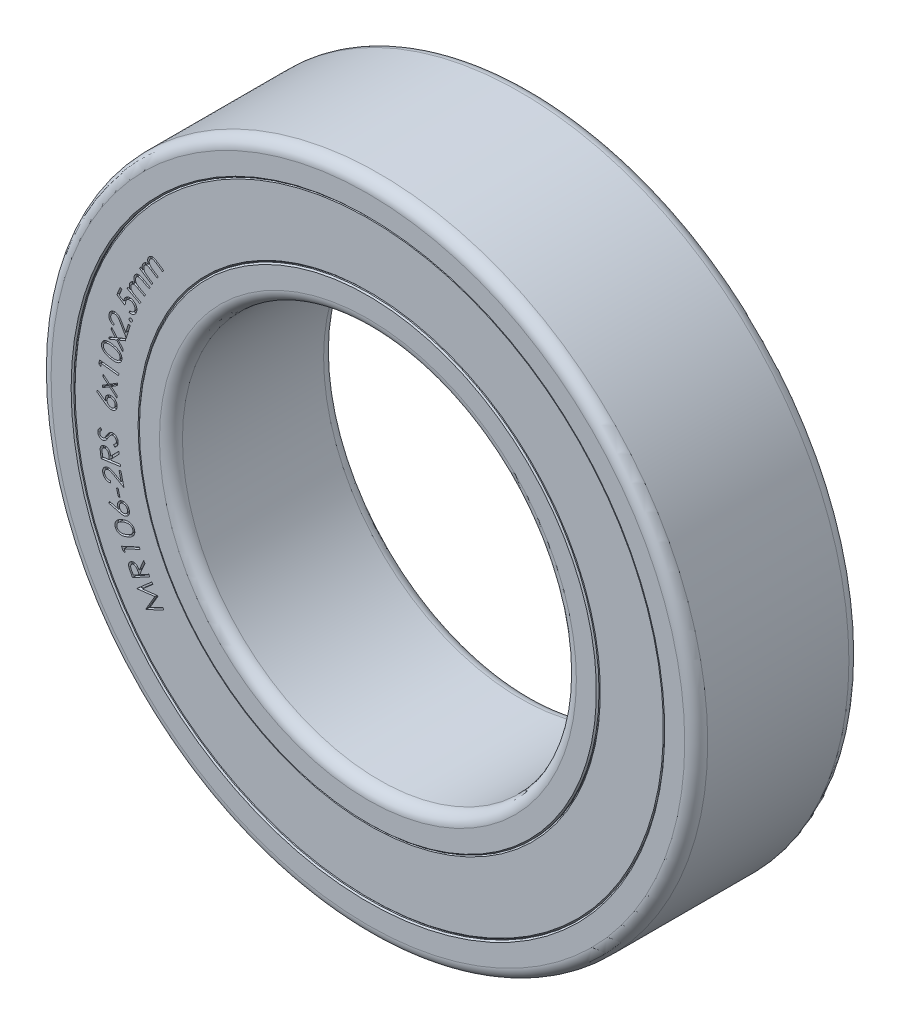
SolidWorks part; units mm, degrees
material "AISI 316 Annealed Stainless Steel Bar (SS)"
ref_plane "Front" through (0, 0, 0) normal (0, 0, 1) x (1, 0, 0)
ref_plane "Top" through (0, 0, 0) normal (0, 1, 0) x (1, 0, 0)
ref_plane "Right" through (0, 0, 0) normal (1, 0, 0) x (0, 0, -1)
sketch "LAYOUT R" plane through (0, 0, 0) normal (1, 0, 0) x (0, 0, -1)
  line L0 (-1.25, 3) -> (1.25, 3)
  line L1 (1.25, -5) -> (-1.25, -5) construction
  line L2 (1.25, -5) -> (1.25, 5) construction
  line L3 (1.25, 5) -> (-1.25, 5)
  line L4 (-1.25, -5) -> (-1.25, 5) construction
  line L5 (1.25, -5) -> (-1.25, 5) construction
  line L6 (1.25, 5) -> (-1.25, -5) construction
  line L7 (-1.25, 3.5) -> (1.25, 3.5)
  line L8 (-1.25, 4.5) -> (1.25, 4.5)
  line L11 (-17.5, 0) -> (17.5, 0) construction
  line L12 (-1.25, 5) -> (-1.25, 4.5)
  line L13 (1.25, 5) -> (1.25, 4.5)
  line L14 (-1.25, 4.5) -> (-1.25, 3.5)
  line L15 (1.25, 4.5) -> (1.25, 3.5)
  line L16 (-1.25, 3.5) -> (-1.25, 3)
  line L17 (1.25, 3.5) -> (1.25, 3)
  line L18 (-1.23, 4.5) -> (-1.23, 3.5)
  line L19 (1.23, 4.5) -> (1.23, 3.5)
  point P0 (0, 0)
  point P15 (0, 0)
  dimension "D1" = 2.5
  dimension "D2" = 10
  dimension "D3" = 3
  dimension "D6" = 0.02
  dimension "D7" = 0.02
  dimension "D4" = 3.5
  dimension "D5" = 4.5
sketch "Sketch R, INNER BODY" plane through (0, 0, 0) normal (1, 0, 0) x (0, 0, -1)
  line L0 (-1.25, 3) -> (1.25, 3) construction
  line L2 (-1.25, 3.5) -> (1.25, 3.5) construction
  line L4 (-1.25, 3) -> (1.25, 3)
  line L6 (-1.25, 3.5) -> (1.25, 3.5)
  line L8 (1.25, 3.5) -> (1.25, 3) construction
  line L9 (-1.25, 3.5) -> (-1.25, 3) construction
  line L10 (1.25, 3.5) -> (1.25, 3)
  line L11 (-1.25, 3.5) -> (-1.25, 3)
  line L12 (-17.5, 0) -> (17.5, 0) construction
  line L13 (-17.5, 0) -> (17.5, 0) construction
sketch "Sketch R, OUTER BODY" plane through (0, 0, 0) normal (1, 0, 0) x (0, 0, -1)
  line L2 (-1.25, 4.5) -> (1.25, 4.5) construction
  line L3 (1.25, 5) -> (-1.25, 5) construction
  line L6 (-1.25, 4.5) -> (1.25, 4.5)
  line L7 (1.25, 5) -> (-1.25, 5)
  line L8 (-17.5, 0) -> (17.5, 0) construction
  line L9 (-17.5, 0) -> (17.5, 0) construction
  line L10 (1.25, 5) -> (1.25, 4.5) construction
  line L11 (-1.25, 5) -> (-1.25, 4.5) construction
  line L12 (1.25, 5) -> (1.25, 4.5)
  line L13 (-1.25, 5) -> (-1.25, 4.5)
sketch "Sketch R, SEAL FACES" plane through (0, 0, 0) normal (1, 0, 0) x (0, 0, -1)
  line L0 (-17.5, 0) -> (17.5, 0) construction
  line L1 (-17.5, 0) -> (17.5, 0) construction
  line L3 (-1.25, 3.5) -> (1.25, 3.5) construction
  line L5 (-1.25, 4.5) -> (1.25, 4.5) construction
  line L7 (-1.23, 3.5) -> (1.23, 3.5)
  line L9 (-1.23, 4.5) -> (1.23, 4.5)
  line L10 (1.23, 4.5) -> (1.23, 3.5) construction
  line L11 (-1.23, 4.5) -> (-1.23, 3.5) construction
  line L12 (1.23, 4.5) -> (1.23, 3.5)
  line L13 (-1.23, 4.5) -> (-1.23, 3.5)
revolve "Revolve INNER BODY" add sketch "Sketch R, INNER BODY" angle 360 about L13
fillet "Fillet INNER BODY" radius 0.175 2 edges at (3, 0, 1.25) (3, 0, -1.25)
chamfer "Chamfer INNER BODY" distance 0.02 angle 45 2 edges at (3.5, 0, -1.25) (3.5, 0, 1.25)
revolve "Revolve OUTER BODY" add sketch "Sketch R, OUTER BODY" angle 360 about L9
fillet "Fillet OUTER BODY" radius 0.175 2 edges at (5, 0, -1.25) (5, 0, 1.25)
chamfer "Chamfer OUTER BODY" distance 0.02 angle 45 2 edges at (4.5, 0, 1.25) (4.5, 0, -1.25)
revolve "Revolve SEALS" add sketch "Sketch R, SEAL FACES" angle 360 about L1
chamfer "Chamfer SEALS" distance 0.02 angle 45 4 edges at (3.5, 0, -1.23) (4.5, 0, -1.23) (4.5, 0, 1.23) (3.5, 0, 1.23)
sketch "Sketch TEXT RADIUS 1 — MANUALLY ASSIGN TEXT AND FONT SIZE (FROM EQUATIONS)" plane through (0, 0, 1.23) normal (0, 0, 1) x (1, 0, 0)
  circle A0 centre (0, 0) radius 3.85 construction
  text T0 "MR106-2RS  6x10x2.5mm" font "Century Gothic" height 0.3
  dimension "D1" = 7.7
extrude "Cut-Extrude SEAL LABEL 1" cut sketch "Sketch TEXT RADIUS 1 — MANUALLY ASSIGN TEXT AND FONT SIZE (FROM EQUATIONS)" against normal blind 0.05
sketch "Sketch TEXT RADIUS 2 — MANUALLY ASSIGN TEXT AND FONT SIZE (FROM EQUATIONS)" plane through (0, 0, -1.23) normal (0, 0, -1) x (-1, 0, 0)
  circle A0 centre (0, 0) radius 3.85 construction
  text T0 "MR106-2RS  6x10x2.5mm" font "Century Gothic" height 0.3
  dimension "D1" = 7.7
extrude "Cut-Extrude SEAL LABEL 2" cut sketch "Sketch TEXT RADIUS 2 — MANUALLY ASSIGN TEXT AND FONT SIZE (FROM EQUATIONS)" against normal blind 0.05
equation "\"_i__BORE\"= 6"
equation "\"_i__OUTSIDE_DIAMETER\"= 10"
equation "\"_i__WIDTH\"= 2.5"
equation "\"_i_optional__TEXT_RADIUS_ADJUSTMENT\"= 0"
equation "\"_output__FONT_SIZE_mm\"= \"BODY_SPAN__SEAL__OF_RADIUS\" * \"param__FONT_SIZE_RATIO\"'MANUALLY ASSIGN TO FONT"
equation "\"BODY__HALF_WIDTH\"= \"_i__WIDTH\" / 2"
equation "\"BODY_SPAN___OF_DIAMETER\"= \"_i__OUTSIDE_DIAMETER\" - \"_i__BORE\""
equation "\"BODY_SPAN___OF_RADIUS\"= \"BODY_SPAN___OF_DIAMETER\" / 2"
equation "\"BODY_SPAN__BORE_AND_OD__OF RADIUS\"= ( \"BODY_SPAN___OF_RADIUS\" - \"BODY_SPAN__SEAL__OF_RADIUS\" ) / 2"
equation "\"BODY_SPAN__SEAL__OF_RADIUS\"= \"BODY_SPAN___OF_RADIUS\" * \"param__SEAL_PANEL_SPAN__RATIO_OF_BODY_RADIAN\""
equation "\"BORE__RADIUS\"= \"_i__BORE\" / 2"
equation "\"CORNER_RADII\"= \"_i__WIDTH\" * \"param__CORNER_RADII__ISO_MAX_RATIO_TO_WIDTH\""
equation "\"param__CORNER_RADII__ISO_MAX_RATIO_TO_WIDTH\"= 0.07'WHERE WIDTH IS LESS THAN DIAMETER"
equation "\"param__FONT_SIZE_RATIO\"= 0.3"
equation "\"param__SEAL_FACE_INSET__RATIO_OF_WIDTH\"= .01"
equation "\"param__SEAL_PANEL_SPAN__RATIO_OF_BODY_RADIAN\"= 0.5"
equation "\"param__SIDE_CHAMFERS__RATIO_TO_OD\"= 1 / 500"
equation "\"RING_INNER__OUTSIDE_RADIUS\"= \"BORE__RADIUS\" + \"BODY_SPAN__BORE_AND_OD__OF RADIUS\""
equation "\"RING_OUTER__OUTSIDE_RADIUS\"= ( \"_i__OUTSIDE_DIAMETER\" / 2 ) - \"BODY_SPAN__BORE_AND_OD__OF RADIUS\""
equation "\"SEAL_FACE_INSET\"= \"_i__WIDTH\" * \"param__SEAL_FACE_INSET__RATIO_OF_WIDTH\""
equation "\"SIDE_FACE_AND_SEAL_CHAMFERS\"= \"_i__OUTSIDE_DIAMETER\" * \"param__SIDE_CHAMFERS__RATIO_TO_OD\""
equation "\"TEXT_RADIUS\"= \"_i__BORE\" + ( \"BODY_SPAN___OF_DIAMETER\" / 2 ) - \"_output__FONT_SIZE_mm\" + \"_i_optional__TEXT_RADIUS_ADJUSTMENT\""
equation "\"D1@Chamfer INNER BODY\"=\"SIDE_FACE_AND_SEAL_CHAMFERS\""
equation "\"D1@Chamfer OUTER BODY\"=\"SIDE_FACE_AND_SEAL_CHAMFERS\""
equation "\"D1@Chamfer SEALS\"=\"SIDE_FACE_AND_SEAL_CHAMFERS\""
equation "\"D1@Fillet INNER BODY\"=\"CORNER_RADII\""
equation "\"D1@Fillet OUTER BODY\"=\"CORNER_RADII\""
equation "\"D1@LAYOUT R\"=\"_i__WIDTH\""
equation "\"D1@Sketch TEXT RADIUS 1 — MANUALLY ASSIGN TEXT AND FONT SIZE (FROM EQUATIONS)\" = \"TEXT_RADIUS\""
equation "\"D1@Sketch TEXT RADIUS 2 — MANUALLY ASSIGN TEXT AND FONT SIZE (FROM EQUATIONS)\" = \"TEXT_RADIUS\""
equation "\"D2@LAYOUT R\"=\"_i__OUTSIDE_DIAMETER\""
equation "\"D3@LAYOUT R\"=\"BORE__RADIUS\""
equation "\"D4@LAYOUT R\"=\"RING_INNER__OUTSIDE_RADIUS\""
equation "\"D5@LAYOUT R\"=\"RING_OUTER__OUTSIDE_RADIUS\""
